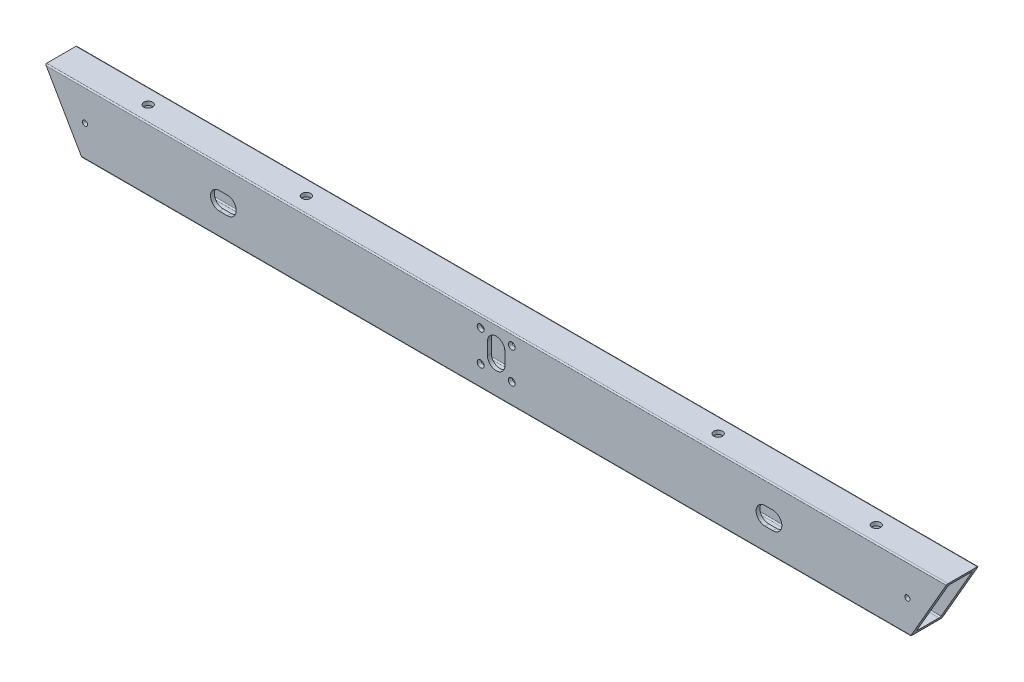
SolidWorks part; units mm, degrees
ref_plane "Front Plane" through (0, 0, 0) normal (0, 0, 1) x (1, 0, 0)
ref_plane "Top Plane" through (0, 0, 0) normal (0, 1, 0) x (1, 0, 0)
ref_plane "Right Plane" through (0, 0, 0) normal (1, 0, 0) x (0, 0, -1)
sketch "Sketch2" plane through (0, 0, 0) normal (0, 0, 1) x (1, 0, 0)
  line L0 (-332.6206, -25.4) -> (-361.95, 25.4)
  line L1 (-361.95, 25.4) -> (361.95, 25.4)
  line L3 (-332.6206, -25.4) -> (332.6206, -25.4)
  line L5 (0, 25.4) -> (0, -25.4) construction
  line L8 (332.6206, -25.4) -> (361.95, 25.4)
  point P0 (0, 0)
  point P4 (0, 0)
  point P8 (0, 25.4)
  dimension "D1" = 50.8
  dimension "D2" = 60
  dimension "D3" = 723.9
extrude "Boss-Extrude1" add sketch "Sketch2" along normal mid plane 25.4 contours L1 L8 L3 L0
sketch "Sketch3" plane through (0, 0, 0) normal (1, 0, 0) x (0, 0, -1)
  line L12 (9.652, -22.352) -> (9.652, 22.352)
  line L13 (-9.652, -22.352) -> (9.652, -22.352)
  line L14 (-9.652, 22.352) -> (-9.652, -22.352)
  line L15 (9.652, 22.352) -> (-9.652, 22.352)
  line L16 (9.652, -22.352) -> (9.652, 22.352)
  line L17 (-9.652, -22.352) -> (9.652, -22.352)
  line L18 (-9.652, 22.352) -> (-9.652, -22.352)
  line L19 (9.652, 22.352) -> (-9.652, 22.352)
  dimension "D1" = 3.048
extrude "Cut-Extrude1" cut sketch "Sketch3" against normal through all and the other way through all contours L16 L19 L18 L17
fillet "Fillet1" radius 1 8 edges at (0, 22.352, 9.652) (0, 22.352, -9.652) (0, -22.352, -9.652) (0, -22.352, 9.652) (0, -25.4, -12.7) (0, -25.4, 12.7) (0, 25.4, -12.7) (0, 25.4, 12.7)
sketch "Sketch4" plane through (0, 0, -12.7) normal (0, 0, -1) x (-1, 0, 0)
  line L1 (7, 0) -> (7, 10)
  line L2 (-7, 0) -> (-7, 10)
  arc A0 (-7, 0) -> (7, 0) centre (0, 0) ccw
  arc A1 (7, 10) -> (-7, 10) centre (0, 10) ccw
  dimension "D1" = 14
  dimension "D2" = 10
extrude "Cut-Extrude2" cut sketch "Sketch4" against normal up to next
sketch "Sketch5" plane through (0, 0, 12.7) normal (0, 0, 1) x (1, 0, 0)
  line L0 (15.875, 4) -> (-15.875, 4) construction
  line L1 (14.875, -11.875) -> (-14.875, -11.875)
  line L2 (15.875, -10.875) -> (15.875, 18.875)
  line L3 (14.875, 19.875) -> (-14.875, 19.875)
  line L4 (-15.875, -10.875) -> (-15.875, 18.875)
  arc A0 (-14.875, -11.875) -> (-15.875, -10.875) centre (-14.875, -10.875) cw
  arc A1 (14.875, -11.875) -> (15.875, -10.875) centre (14.875, -10.875) ccw
  arc A2 (15.875, 18.875) -> (14.875, 19.875) centre (14.875, 18.875) ccw
  arc A3 (-14.875, 19.875) -> (-15.875, 18.875) centre (-14.875, 18.875) ccw
  point P1 (0, 19.875)
  dimension "D2" = 1
  dimension "D1" = 31.75
  dimension "D3" = 4
extrude "Cut-Extrude3" cut sketch "Sketch5" against normal up to next
hole_wizard "M5 Clearance Hole1" positions "Sketch12" profile "Sketch7" hole size "M5" standard "ANSI Metric" end condition up to next
sketch "Sketch12" [suppressed] plane through (0, 0, -9.652) normal (0, 0, 1) x (1, 0, 0)
  line L1 (12.5, 16.5) -> (12.5, -8.5) construction
  line L2 (12.5, -8.5) -> (-12.5, -8.5) construction
  circle A5 centre (-12.5, 16.5) radius 2.1 construction
  point P0 (-12.5, 16.5)
  point P2 (12.5, 16.5)
  point P4 (12.5, -8.5)
  point P6 (-12.5, -8.5)
  point P47 (0, -8.5)
  dimension "D1" = 25
  dimension "D2" = 25
sketch "Sketch7" plane through (-12.5, 16.5, -9.652) normal (1, 0, 0) x (0, -1, 0)
  line L0 (0, 0) -> (0, 3.048)
  line L1 (0, 3.048) -> (2.75, 3.048)
  line L2 (2.75, 3.048) -> (2.75, 0)
  line L5 (2.75, 0) -> (0, 0)
  line L11 (0, -6.35) -> (0, 107.95) construction
  dimension "Thru Hole Dia." = 5.5
  dimension "Thru Hole Depth" = 3.048
sketch "Sketch9" plane through (0, 0, -12.7) normal (0, 0, -1) x (-1, 0, 0)
  line L0 (-222.25, 0) -> (-215.9, 0) construction
  line L1 (-222.25, 7.1437) -> (-215.9, 7.1437)
  line L2 (-222.25, -7.1437) -> (-215.9, -7.1437)
  line L3 (0, 13.97) -> (0, -13.97) construction
  line L4 (222.25, 0) -> (215.9, 0) construction
  line L5 (222.25, 7.1437) -> (215.9, 7.1437)
  line L6 (222.25, -7.1437) -> (215.9, -7.1437)
  arc A0 (-222.25, 7.1437) -> (-222.25, -7.1437) centre (-222.25, 0) ccw
  arc A1 (-215.9, -7.1437) -> (-215.9, 7.1437) centre (-215.9, 0) ccw
  arc A2 (222.25, 7.1437) -> (222.25, -7.1437) centre (222.25, 0) cw
  arc A3 (215.9, -7.1437) -> (215.9, 7.1437) centre (215.9, 0) cw
  point P2 (-219.075, 0)
  point P12 (219.075, 0)
  dimension "D2" = 14.2875
  dimension "D1" = 6.35
  dimension "D3" = 215.9
extrude "Wire Slots" cut sketch "Sketch9" against normal up to next
sketch "Sketch14" plane through (0, 25.4, 0) normal (0, 1, 0) x (1, 0, 0)
  line L0 (-165.35, -0.2) -> (-292.35, -0.2) construction
  line L1 (165.35, -0.2) -> (292.35, -0.2) construction
  line L4 (0, 0) -> (0, 11.7) construction
  line L5 (361.95, 11.7) -> (-361.95, 11.7) construction
  circle A0 centre (-165.35, -0.2) radius 3.5
  circle A2 centre (-292.35, -0.2) radius 3.5
  circle A8 centre (-165.35, -0.2) radius 2.75 construction
  circle A9 centre (-292.35, -0.2) radius 2.75 construction
  circle A10 centre (292.35, -0.2) radius 3.5
  circle A11 centre (165.35, -0.2) radius 3.5
  dimension "D1" = 7
  dimension "D2" = 165.3501
  dimension "D3" = 127
extrude "Plate Mounting" cut sketch "Sketch14" against normal up to next
hole_wizard "M5x0.8 Tapped Hole1" positions "Sketch26" profile "Sketch25" tap size "M5x0.8" standard "ANSI Metric" end condition up to next
sketch "Sketch26" plane through (0, 0, -38.1) normal (0, 0, -1) x (-1, 0, 0)
  line L0 (0, 0) -> (0, -24.4) construction
  line L1 (333.198, -24.4) -> (-333.198, -24.4) construction
  point P0 (-330.2, 0)
  point P2 (330.2, 0)
  dimension "D1" = 330.2
sketch "Sketch25" plane through (330.2, 0, -38.1) normal (1, 0, 0) x (0, 1, 0)
  line L0 (0, 0) -> (0, 28.448)
  line L1 (0, 28.448) -> (2.1, 28.448)
  line L2 (2.1, 28.448) -> (2.1, 0)
  line L5 (2.1, 0) -> (0, 0)
  line L11 (0, -6.35) -> (0, 107.95) construction
  dimension "Thru Tap Drill Dia." = 4.2
  dimension "Thru Tap Drill Depth" = 28.448
mirror "Mirror1" about plane through (0, 0, -12.7) normal (0, 0, -1) of bodies 114 106
sketch "Sketch10" plane through (0, 0, 0) normal (1, 0, 0) x (0, 0, -1)
  line L0 (-12.7, -24.4) -> (-12.7, 24.4) construction
  line L1 (12.7, -25.4) -> (-12.7, -25.4)
  line L2 (12.7, -25.4) -> (12.7, 25.4)
  line L3 (12.7, 25.4) -> (-12.7, 25.4)
  line L4 (-12.7, -25.4) -> (-12.7, 25.4)
  line L5 (12.7, -25.4) -> (-12.7, 25.4) construction
  line L6 (12.7, 25.4) -> (-12.7, -25.4) construction
  line L7 (-11.7, 25.4) -> (11.7, 25.4) construction
  point P0 (0, 0)
extrude "Cut-Extrude5" cut sketch "Sketch10" against normal through all both and the other way through all
sketch "Sketch15" [suppressed] plane through (0, 0, 12.7) normal (0, 0, 1) x (1, 0, 0)
  circle A0 centre (279.4, 0) radius 11.75
  dimension "D1" = 23.5
  dimension "D2" = 279.4
extrude "Charging" [suppressed] cut sketch "Sketch15" against normal up to next
hole_wizard "Power" positions "Sketch19" profile "Sketch18" hole size "M16" standard "ANSI Metric" end condition up to next
sketch "Sketch19" plane through (0, 0, -38.1) normal (0, 0, -1) x (-1, 0, 0)
  point P0 (266.7, 0)
  dimension "D1" = 266.7
sketch "Sketch18" plane through (-266.7, 0, -38.1) normal (1, 0, 0) x (0, 1, 0)
  line L0 (0, 0) -> (0, 3.048)
  line L1 (0, 3.048) -> (8, 3.048)
  line L2 (8, 3.048) -> (8, 0)
  line L5 (8, 0) -> (0, 0)
  line L11 (0, -6.35) -> (0, 107.95) construction
  dimension "Thru Hole Dia." = 16
  dimension "Thru Hole Depth" = 3.048
sketch "Sketch23" plane through (0, 0, -12.7) normal (0, 0, 1) x (1, 0, 0)
  line L0 (0, 0) -> (0, 25.0615) construction
  point P0 (330.2, 0)
  point P9 (-330.2, 0)
  dimension "D1" = 330.2
equation "\"Length\"= 28.5"
equation "\"D3@Sketch2\"=\"Length\""
